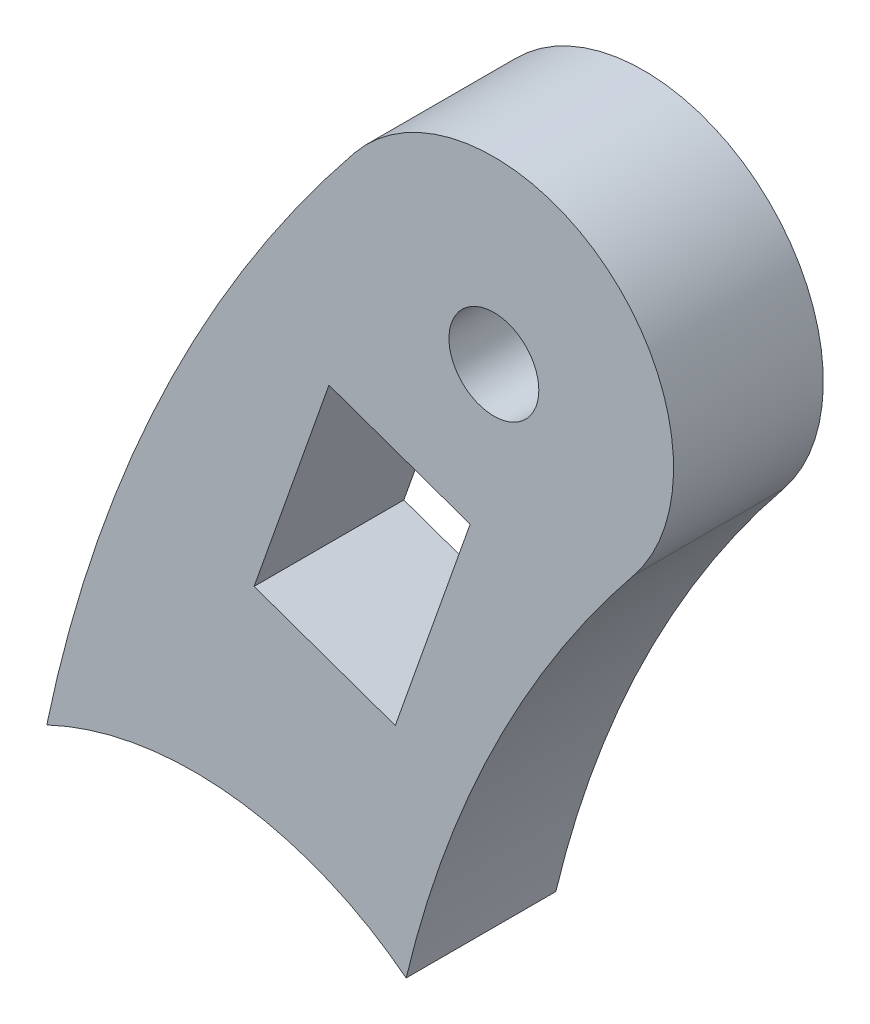
SolidWorks part; units mm, degrees
ref_plane "Plan de face" through (0, 0, 0) normal (0, 0, 1) x (1, 0, 0)
ref_plane "Plan de dessus" through (0, 0, 0) normal (0, 1, 0) x (1, 0, 0)
ref_plane "Plan de droite" through (0, 0, 0) normal (1, 0, 0) x (0, 0, -1)
sketch "Esquisse1" plane through (0, 0, 0) normal (0, 0, 1) x (1, 0, 0)
  line L0 (-35, 28.2843) -> (0, 0) construction
  line L1 (0, 0) -> (-45, 0) construction
  line L2 (-47.0298, -1.0204) -> (-35.9733, 30.2522) construction
  line L3 (0, 0) -> (-42.4264, 15) construction
  line L4 (-43.0073, 17.857) -> (-38.2932, 16.1904)
  line L5 (-38.2932, 16.1904) -> (-35.7932, 23.2614)
  line L6 (-35.7932, 23.2614) -> (-40.5073, 24.9281)
  line L7 (-40.5073, 24.9281) -> (-43.0073, 17.857)
  arc A0 (-45, 0) -> (-35, 28.2843) centre (0, 0) cw construction
  arc A1 (-39.6667, 32.0555) -> (-49.9306, 10.3894) centre (0, 0) ccw
  arc A2 (-30.3333, 24.513) -> (-37.9306, 9.0704) centre (0, 0) ccw
  arc A3 (-30.3333, 24.513) -> (-39.6667, 32.0555) centre (-35, 28.2843) ccw
  arc A4 (-49.9306, 10.3894) -> (-37.9306, 9.0704) centre (-45, 0) cw
  circle A5 centre (-35, 28.2843) radius 1.5
  circle A6 centre (-45, 0) radius 1.5 construction
  circle A7 centre (-45, 0) radius 11.5 construction
  dimension "D1" = 30
  dimension "D2" = 3
  dimension "D3" = 6
  dimension "D4" = 45
  dimension "D6" = 23
  dimension "D7" = 51
  dimension "D8" = 39
  dimension "D5" = 1
  dimension "D9" = 2.5
  dimension "D10" = 7.5
  dimension "D11" = 5
extrude "Boss.-Extru.1" add sketch "Esquisse1" along normal blind 5
